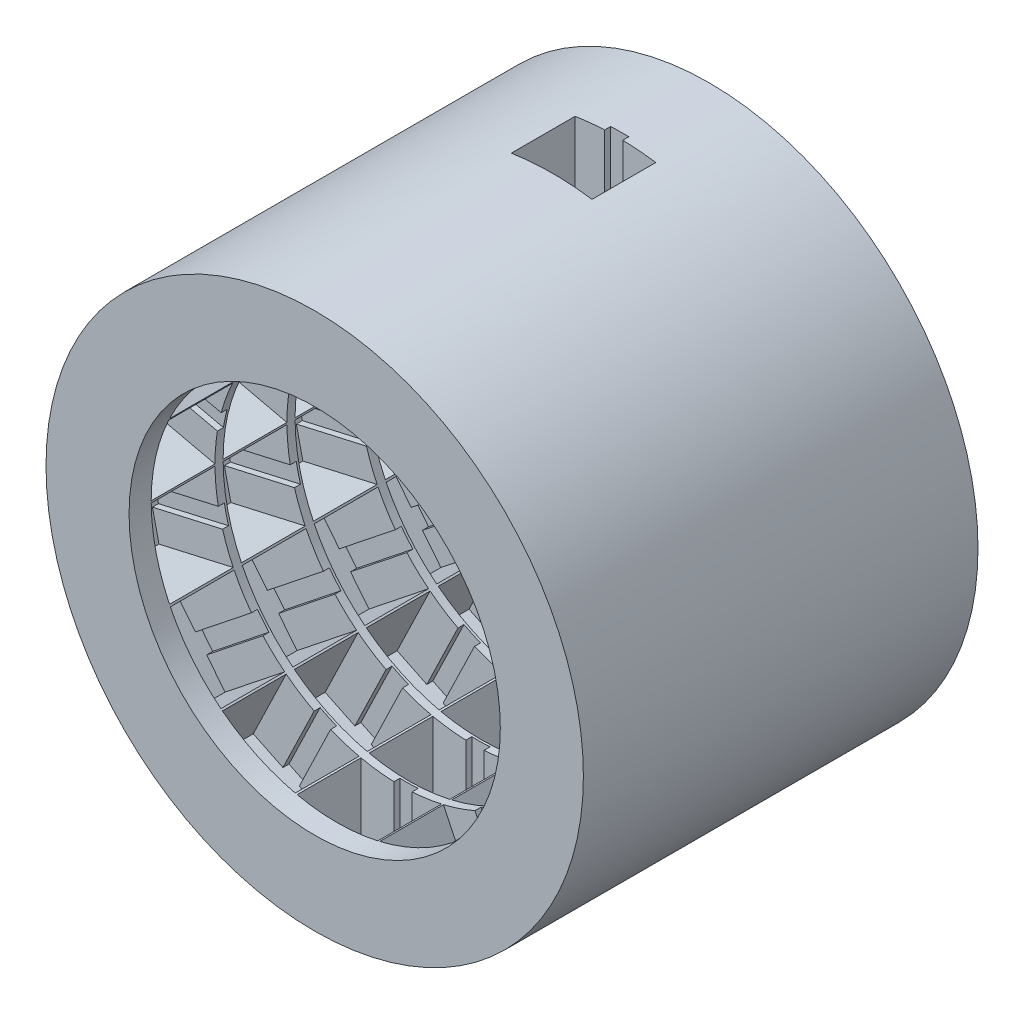
SolidWorks part; units mm, degrees
ref_plane "Front Plane" through (0, 0, 0) normal (0, 0, 1) x (1, 0, 0)
ref_plane "Top Plane" through (0, 0, 0) normal (0, 1, 0) x (1, 0, 0)
ref_plane "Right Plane" through (0, 0, 0) normal (1, 0, 0) x (0, 0, -1)
sketch "Sketch1" plane through (0, 0, 943.5108) normal (0, 0, 1) x (1, 0, 0)
  circle A0 centre (833.9306, -1197.1664) radius 1419.273
  circle A1 centre (833.9306, -1197.1664) radius 2054.3259
extrude "Boss-Extrude1" add sketch "Sketch1" along normal blind 3017 contours A1 A0 region at (-1162.2902, -1197.1664, 943.5108)
sketch "Sketch2" plane through (0, 0, 0) normal (0, 1, 0) x (1, 0, 0)
  line L0 (1134.8675, -1653.6882) -> (882.6171, -1653.6882)
  line L1 (1134.8675, -2141.4099) -> (518.1595, -2141.4099)
  line L2 (1134.8675, -2141.4099) -> (1134.8675, -1653.6882)
  line L4 (518.1595, -2141.4099) -> (518.1595, -1653.6882)
  line L6 (882.6171, -1653.6882) -> (882.6171, -1607.727)
  line L7 (882.6171, -1607.727) -> (743.6842, -1607.727)
  line L8 (743.6842, -1653.6882) -> (743.6842, -1607.727)
  line L9 (743.6842, -1653.6882) -> (518.1595, -1653.6882)
extrude "Cut-Extrude1" cut sketch "Sketch2" along normal blind 769
pattern_circular "CirPattern1" count 14 every 25.7 about axis through (833.9306, -1197.1664, 3960.5108) along (0, 0, -1) of "Cut-Extrude1" reverse direction yes
pattern_linear "LPattern1" count 2 spacing 550 along (0, 0, -1) of "CirPattern1"
pattern_linear "LPattern2" count 4 spacing 550 along (0, 0, 1) of "CirPattern1"
extrude "Cut-Extrude4" cut sketch "Sketch2<2>" along normal blind 1203
sketch "Sketch2<2>" plane through (0, 0, 0) normal (0, 1, 0) x (1, 0, 0) same geometry as "Sketch2"
